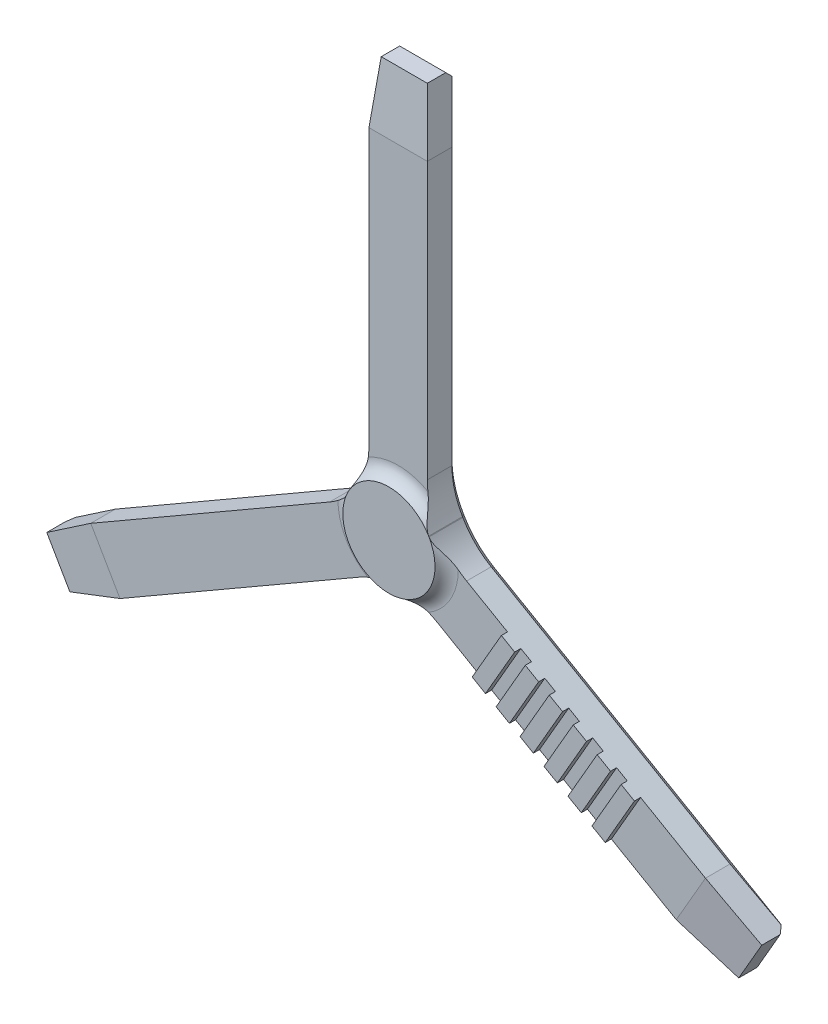
SolidWorks part; units mm, degrees
ref_plane "Front Plane" through (0, 0, 0) normal (0, 0, 1) x (1, 0, 0)
ref_plane "Top Plane" through (0, 0, 0) normal (0, 1, 0) x (1, 0, 0)
ref_plane "Right Plane" through (0, 0, 0) normal (1, 0, 0) x (0, 0, -1)
sketch "Sketch1" plane through (0, 0, 0) normal (0, 0, 1) x (1, 0, 0)
  line L0 (-1.9, 24) -> (1.9, 24) construction
  line L1 (0, 0) -> (0, 24) construction
  line L2 (-1.9, 24) -> (-1.9, 26)
  line L3 (-1.9, 26) -> (1.9, 26)
  line L4 (1.9, 26) -> (1.9, 24)
  line L5 (23.4667, -11.3546) -> (21.5667, -14.6454)
  line L6 (21.5667, -14.6454) -> (19.8346, -13.6454)
  line L7 (21.7346, -10.3546) -> (23.4667, -11.3546)
  line L8 (-21.5667, -14.6454) -> (-23.4667, -11.3546)
  line L9 (-23.4667, -11.3546) -> (-21.7346, -10.3546)
  line L10 (-19.8346, -13.6454) -> (-21.5667, -14.6454)
  line L11 (0, 0) -> (1.9, 24) construction
  line L12 (0, 0) -> (19.8346, -13.6454) construction
  line L13 (-1.9, 24) -> (-1.9, 1.097)
  line L14 (-1.9, 1.097) -> (-21.7346, -10.3546)
  line L15 (-19.8346, -13.6454) -> (0, -2.1939)
  line L16 (0, -2.1939) -> (19.8346, -13.6454)
  line L17 (21.7346, -10.3546) -> (1.9, 1.097)
  line L18 (1.9, 1.097) -> (1.9, 24)
  circle A0 centre (0, 0) radius 24 construction
  dimension "D1" = 48
  dimension "D2" = 3.8
  dimension "D3" = 2
  dimension "D4" = 120
  dimension "D5" = 24.0751
  dimension "D6" = 3
extrude "Boss-Extrude1" add sketch "Sketch1" along normal blind 2 contours L18 A0 L13 L14 L15 L16 L17 region at (0, 0, 0)
chamfer "Chamfer1" distance 4 distance2 0.4 3 edges at (22.5167, -13, 2) (-22.5167, -13, 2) (0, 26, 2) first distance on face at (0, 0, 2)
chamfer "Chamfer2" distance 0.4 distance2 4 3 edges at (23.4667, -11.3546, 0.8) (-1.9, 26, 0.8) (-21.5667, -14.6454, 0.8) first distance on face at (22.5167, -13, 0.8) first distance on face at (0, 26, 0.8) first distance on face at (-22.5167, -13, 0.8)
chamfer "Chamfer3" distance 4 distance2 0.4 3 edges at (1.9, 26, 0.8) (21.5667, -14.6454, 0.8) (-23.4667, -11.3546, 0.8) first distance on face at (1.9, 15.2388, 1.12) first distance on face at (12.2472, -9.2648, 1.12) first distance on face at (-14.1472, -5.9739, 1.12)
sketch "Sketch2" plane through (0, 0, 0) normal (0, 0, -1) x (-1, 0, 0)
  circle A0 centre (0, 0) radius 3
  dimension "D1" = 6
extrude "Boss-Extrude2" add sketch "Sketch2" against normal blind 2.6
fillet "Fillet1" radius 5 6 edges at (1.9, 2.3216, 1) (2.9606, 0.4846, 1) (1.0606, -2.8063, 1) (-1.0606, -2.8063, 1) (-2.9606, 0.4846, 1) (-1.9, 2.3216, 1)
fillet "Fillet2" radius 1 3 edges at (0, 3, 2) (2.5981, -1.5, 2) (-2.5981, -1.5, 2)
chamfer "Chamfer4" distance 0.4 angle 45 18 edges at (22.5167, -13, 0) (-22.5167, -13, 0) (0, 26, 0) (12.2293, -4.8667, 0) (3.4082, 0.4282, 0) (2.5981, 1.5, 0) (2.0749, 2.7374, 0) (1.9, 13.0242, 0) (-12.2293, -4.8667, 0) (-3.4082, 0.4282, 0) (-2.5981, 1.5, 0) (-2.0749, 2.7374, 0) (-1.9, 13.0242, 0) (10.3293, -8.1576, 0) (1.3332, -3.1657, 0) (0, -3, 0) (-1.3332, -3.1657, 0) (-10.3293, -8.1576, 0)
sketch "Sketch3" plane through (0, 0, 2) normal (0, 0, 1) x (1, 0, 0)
  line L0 (12.2293, -4.8667) -> (10.3293, -8.1576) construction
  line L3 (20.0026, -9.3546) -> (4.4561, -0.3788) construction
  line L5 (2.5561, -3.6697) -> (18.1026, -12.6454) construction
  line L7 (11.7963, -4.6167) -> (9.8963, -7.9076)
  line L8 (11.7963, -4.6167) -> (12.6623, -5.1167)
  line L9 (9.8963, -7.9076) -> (10.7623, -8.4076)
  line L10 (12.6623, -5.1167) -> (10.7623, -8.4076)
  line L11 (11.7963, -4.6167) -> (10.7623, -8.4076) construction
  line L12 (9.8963, -7.9076) -> (12.6623, -5.1167) construction
  line L13 (13.3551, -5.5167) -> (14.2212, -6.0167)
  line L14 (13.3551, -5.5167) -> (11.4551, -8.8076)
  line L15 (14.2212, -6.0167) -> (12.3212, -9.3076)
  line L16 (11.4551, -8.8076) -> (12.3212, -9.3076)
  line L17 (14.914, -6.4167) -> (15.78, -6.9167)
  line L18 (14.914, -6.4167) -> (13.014, -9.7076)
  line L19 (15.78, -6.9167) -> (13.88, -10.2076)
  line L20 (13.014, -9.7076) -> (13.88, -10.2076)
  line L29 (10.2375, -3.7167) -> (11.1035, -4.2167)
  line L30 (10.2375, -3.7167) -> (8.3375, -7.0076)
  line L31 (11.1035, -4.2167) -> (9.2035, -7.5076)
  line L32 (8.3375, -7.0076) -> (9.2035, -7.5076)
  line L33 (8.6786, -2.8167) -> (9.5446, -3.3167)
  line L34 (8.6786, -2.8167) -> (6.7786, -6.1076)
  line L35 (9.5446, -3.3167) -> (7.6446, -6.6076)
  line L36 (6.7786, -6.1076) -> (7.6446, -6.6076)
  line L37 (7.1198, -1.9167) -> (7.9858, -2.4167)
  line L38 (7.1198, -1.9167) -> (5.2198, -5.2076)
  line L39 (7.9858, -2.4167) -> (6.0858, -5.7076)
  line L40 (5.2198, -5.2076) -> (6.0858, -5.7076)
  line L465 (18.0317, -8.2167) -> (18.8977, -8.7167) [skipped]
  line L466 (18.0317, -8.2167) -> (16.1317, -11.5076) [skipped]
  line L467 (18.8977, -8.7167) -> (16.9977, -12.0076) [skipped]
  line L468 (16.1317, -11.5076) -> (16.9977, -12.0076) [skipped]
  line L469 (5.5609, -1.0167) -> (6.4269, -1.5167) [skipped]
  line L470 (5.5609, -1.0167) -> (3.6609, -4.3076) [skipped]
  line L471 (6.4269, -1.5167) -> (4.5269, -4.8076) [skipped]
  line L472 (3.6609, -4.3076) -> (4.5269, -4.8076) [skipped]
  line L473 (16.4728, -7.3167) -> (17.3389, -7.8167) [skipped]
  line L474 (16.4728, -7.3167) -> (14.5728, -10.6076) [skipped]
  line L475 (17.3389, -7.8167) -> (15.4389, -11.1076) [skipped]
  line L476 (14.5728, -10.6076) -> (15.4389, -11.1076) [skipped]
  point P7 (11.2793, -6.5121)
  dimension "D1" = 1
extrude "Boss-Extrude3" add sketch "Sketch3" along normal blind 0.4
